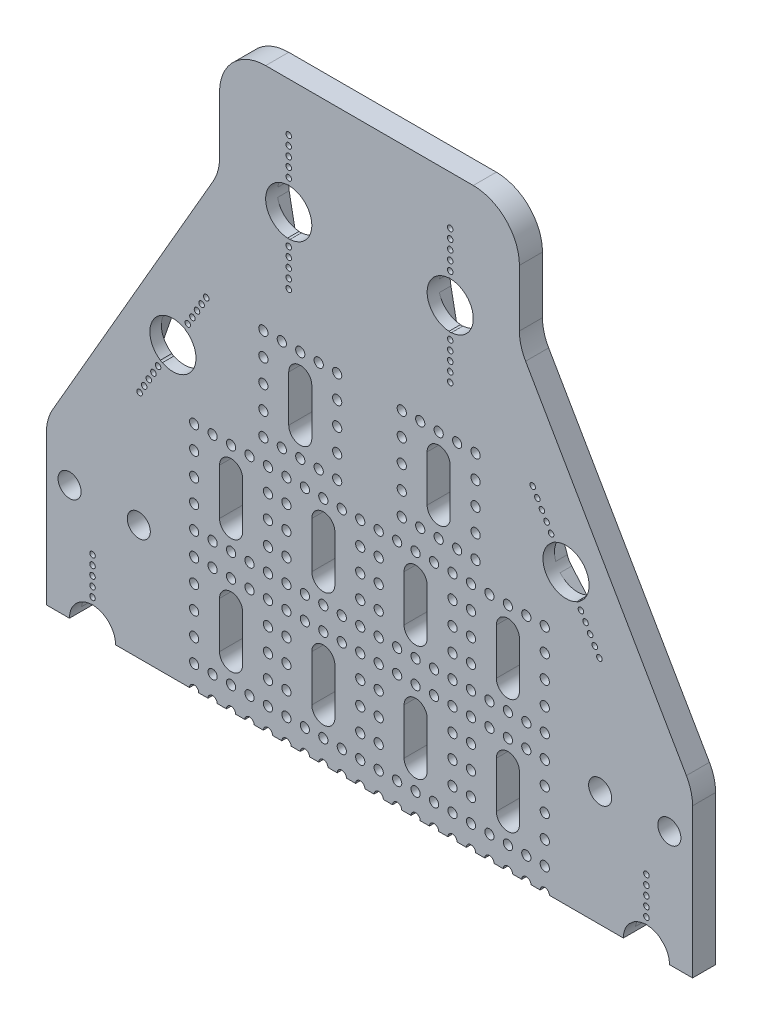
SolidWorks part; units mm, degrees
ref_plane "前视基准面" through (0, 0, 0) normal (0, 0, 1) x (1, 0, 0)
ref_plane "上视基准面" through (0, 0, 0) normal (0, 1, 0) x (1, 0, 0)
ref_plane "右视基准面" through (0, 0, 0) normal (1, 0, 0) x (0, 0, -1)
other "Configuration Table"
sketch "Sketch1" plane through (0, 0, 0) normal (0, 0, 1) x (1, 0, 0)
  line L0 (0, 0) -> (0, 100) construction
  line L1 (-32.5, -100) -> (32.5, -100)
  line L2 (-32.5, -100) -> (-32.5, 100)
  line L3 (-32.5, 100) -> (32.5, 100)
  line L4 (32.5, -100) -> (32.5, 100)
  line L5 (-32.5, -100) -> (32.5, 100) construction
  line L6 (-32.5, 100) -> (32.5, -100) construction
  line L7 (-32.5, 100) -> (-70.0278, 35)
  line L8 (-70.0278, 35) -> (-70.0278, -35)
  line L9 (0, 0) -> (-70.0278, 0) construction
  line L10 (-32.5, -100) -> (-70.0278, -35)
  line L11 (32.5, -100) -> (70.0278, -35)
  line L12 (32.5, 100) -> (70.0278, 35)
  line L13 (70.0278, 35) -> (70.0278, -35)
  point P0 (0, 0)
  dimension "D1" = 65
  dimension "D2" = 200
  dimension "D3" = 35
  dimension "D4" = 30
extrude "Boss-Extrude1" add sketch "Sketch1" along normal mid plane 5 contours L10 L2 L7 L8 | L1 L4 L3 L2 | L13 L12 L4 L11 region at (0, 0, 0) region at (-48.2524, 0, 0) region at (48.2524, 0, 0)
sketch "Sketch2" plane through (0, 0, -2.5) normal (0, 0, -1) x (-1, 0, 0)
  line L0 (0, 0) -> (0, 100) construction
  line L1 (32.5, 100) -> (-32.5, 100) construction
  line L2 (-32.5, 100) -> (-70.0278, 35) construction
  line L3 (-70.0278, 35) -> (-51.2639, 67.5) construction
  line L4 (-51.2639, 67.5) -> (-33.9434, 57.5) construction
  line L5 (-56.7639, 57.9737) -> (-45.7639, 77.0263)
  line L9 (-42.6036, 62.5) -> (-37.1036, 72.0263) construction
  line L10 (0, 0) -> (0, 80) construction
  line L11 (0, 80) -> (20, 80) construction
  line L22 (0, 0) -> (-70.0278, 0) construction
  line L23 (-70.0278, 35) -> (-70.0278, -35) construction
  line L24 (-70.0278, 0) -> (-50.0278, 0) construction
  line L25 (-70.0278, -11) -> (-70.0278, 11)
  line L26 (-70.0278, 11) -> (-50.0278, 11)
  line L27 (-50.0278, 11) -> (-50.0278, 0)
  line L28 (-50.0278, 0) -> (-70.0278, 0) construction
  line L29 (-70.0278, 0) -> (-60.0278, 0) construction
  line L30 (-60.0278, 0) -> (-60.0278, 11) construction
  line L31 (-60.0278, 11) -> (-60.0278, 5.5) construction
  line L32 (-60.0278, 5.5) -> (-50.0278, 5.5) construction
  line L33 (-50.0278, 5.5) -> (-55.0278, 5.5) construction
  line L34 (-50.0278, -5.5) -> (-55.0278, -5.5) construction
  line L35 (-60.0278, -5.5) -> (-50.0278, -5.5) construction
  line L36 (-60.0278, -11) -> (-60.0278, -5.5) construction
  line L37 (-60.0278, 0) -> (-60.0278, -11) construction
  line L38 (-50.0278, -11) -> (-50.0278, 0)
  line L39 (-70.0278, -11) -> (-50.0278, -11)
  circle A8 centre (-55.0278, 5.5) radius 2.5
  circle A9 centre (-55.0278, -5.5) radius 2.5
  circle A10 centre (-65.0278, -5.5) radius 2.5
  circle A11 centre (-65.0278, 5.5) radius 2.5
  circle A84 centre (-42.6036, 62.5) radius 5
  circle A86 centre (-60.0278, 0) radius 5
  circle A87 centre (-42.6036, -62.5) radius 5
  circle A88 centre (42.6036, -62.5) radius 5
  circle A89 centre (60.0278, 0) radius 5
  circle A90 centre (42.6036, 62.5) radius 5
  circle A91 centre (20, 80) radius 5
  circle A93 centre (-20, 80) radius 5
  dimension "D3" = 10
  dimension "D6" = 5
  dimension "D7" = 10
  dimension "D8" = 10
  dimension "D1" = 22
  dimension "D2" = 10
  dimension "D4" = 20
  dimension "D5" = 22
  dimension "D9" = 20
  dimension "D10" = 80
sketch "Sketch3" plane through (0, 0, -2.5) normal (0, 0, -1) x (-1, 0, 0)
  line L0 (0, 0) -> (0, -75) construction
  line L1 (0, -50) -> (0, -75) construction
  line L2 (-25, -100) -> (25, -100)
  line L3 (-25, -100) -> (-25, -50)
  line L4 (-25, -50) -> (25, -50)
  line L5 (25, -100) -> (25, -50)
  line L6 (-25, -100) -> (25, -50) construction
  line L7 (-25, -50) -> (25, -100) construction
  line L8 (0, -75) -> (25, -75) construction
  line L9 (25, -75) -> (12.5, -75) construction
  line L10 (0, -75) -> (17.6777, -57.3223) construction
  circle A4 centre (17.6777, -57.3223) radius 2.5
  circle A5 centre (-17.6777, -57.3223) radius 2.5
  circle A6 centre (17.6777, -92.6777) radius 2.5
  circle A7 centre (-17.6777, -92.6777) radius 2.5
  dimension "D3" = 5
  dimension "D1" = 50
  dimension "D2" = 75
  dimension "D4" = 25
sketch "Sketch5" plane through (0, 0, -2.5) normal (0, 0, -1) x (-1, 0, 0)
  line L0 (0, 0) -> (0, 40) construction
  line L1 (0, 40) -> (30, 40) construction
  line L2 (30, 40) -> (38, 40) construction
  line L3 (27.5, 35) -> (32.5, 35)
  line L4 (27.5, 35) -> (27.5, 45)
  line L5 (27.5, 45) -> (32.5, 45)
  line L6 (32.5, 35) -> (32.5, 45)
  line L7 (27.5, 35) -> (32.5, 45) construction
  line L8 (27.5, 45) -> (32.5, 35) construction
  line L9 (38, 40) -> (38, 50) construction
  line L10 (38, 50) -> (38, 45) construction
  line L11 (30, 40) -> (30, 45) construction
  line L12 (22, 50) -> (22, 45) construction
  line L13 (22, 40) -> (22, 50) construction
  line L14 (22, 50) -> (38, 50) construction
  line L15 (38, 50) -> (30, 50) construction
  line L16 (30, 50) -> (34, 50) construction
  circle A0 centre (30, 45) radius 2.5
  circle A1 centre (30, 35) radius 2.5
  circle A2 centre (38, 50) radius 1
  circle A3 centre (38, 45) radius 1
  circle A4 centre (38, 40) radius 1
  circle A5 centre (38, 35) radius 1
  circle A6 centre (38, 30) radius 1
  circle A7 centre (22, 30) radius 1
  circle A8 centre (22, 35) radius 1
  circle A9 centre (22, 40) radius 1
  circle A10 centre (22, 45) radius 1
  circle A11 centre (22, 50) radius 1
  circle A12 centre (34, 50) radius 1
  circle A13 centre (30, 50) radius 1
  circle A14 centre (26, 50) radius 1
  circle A15 centre (34, 30) radius 1
  circle A16 centre (30, 30) radius 1
  circle A17 centre (26, 30) radius 1
  dimension "D3" = 2
  dimension "D4" = 2
  dimension "D5" = 2
  dimension "D10" = 2
  dimension "D11" = 2
  dimension "D1" = 10
  dimension "D2" = 5
  dimension "D6" = 8
  dimension "D7" = 5
  dimension "D8" = 30
  dimension "D9" = 40
extrude "Cut-Extrude2" cut sketch "Sketch5" against normal blind 5 contours A1 L6 A0 L4 | L5 A0 | A9 | A8 | L3 A1 | L3 A1 | A5 | A3 | A2 | A6 | A14 | A13 | A12 | A15 | A16 | A17 | A0 | A11 | A7 | A4 | A10 region at (-30, 36.061, -2.5) region at (-30, 40, -2.5) region at (-30, 33.939, -2.5) region at (-30, 46.061, -2.5) region at (-38, 50, -2.5) region at (-38, 45, -2.5) region at (-38, 35, -2.5) region at (-38, 30, -2.5) region at (-22, 35, -2.5) region at (-22, 40, -2.5) region at (-34, 50, -2.5) region at (-30, 50, -2.5) region at (-26, 50, -2.5) region at (-34, 30, -2.5) region at (-30, 30, -2.5) region at (-26, 30, -2.5)
pattern_linear "LPattern1" count 4 spacing 20 along (1, 0, 0) of "Cut-Extrude2"
pattern_linear "LPattern2" count 4 spacing 25 along (0, -1, 0) of "LPattern1"
sketch "Sketch9" plane through (0, 0, -2.5) normal (0, 0, -1) x (-1, 0, 0)
  line L0 (-32.5, 100) -> (-32.5, 125)
  line L1 (-32.5, 125) -> (32.5, 125)
  line L2 (32.5, 125) -> (32.5, 100)
  line L3 (-32.5, 100) -> (32.5, 100)
  dimension "D1" = 25
extrude "Boss-Extrude6" add sketch "Sketch9" against normal blind 5
sketch "Sketch12" plane through (0, 0, -2.5) normal (0, 0, -1) x (-1, 0, 0)
  line L0 (-32.5, 125) -> (-32.5, 100) construction
  line L1 (-32.5, 125) -> (-32.5, 100) construction
  line L2 (-32.5, 100) -> (-32.5, 112.5) construction
  line L4 (-32.5, 112.5) -> (-32.5, 125) construction
  line L5 (-32.5, 125) -> (-32.5, 118.75) construction
  line L6 (-32.5, 118.75) -> (-26, 118.75) construction
  line L9 (-26, 118.75) -> (-13, 105.75) construction
  line L10 (-13, 105.75) -> (0, 118.75) construction
  line L11 (0, 118.75) -> (13, 105.75) construction
  line L12 (13, 105.75) -> (26, 118.75) construction
  line L13 (26, 118.75) -> (19.5, 112.25) construction
  circle A23 centre (-26, 118.75) radius 2.5
  circle A24 centre (-26, 105.75) radius 2.5
  circle A25 centre (-13, 118.75) radius 2.5
  circle A26 centre (-13, 105.75) radius 2.5
  circle A27 centre (0, 118.75) radius 2.5
  circle A28 centre (0, 105.75) radius 2.5
  circle A29 centre (13, 118.75) radius 2.5
  circle A30 centre (13, 105.75) radius 2.5
  circle A31 centre (26, 118.75) radius 2.5
  circle A32 centre (26, 105.75) radius 2.5
  circle A33 centre (-19.5, 112.25) radius 2.5
  circle A34 centre (-6.5, 112.25) radius 2.5
  circle A35 centre (6.5, 112.25) radius 2.5
  circle A36 centre (19.5, 112.25) radius 2.5
  dimension "D1" = 5
  dimension "D2" = 6.5
  dimension "D4" = 5
  dimension "D3" = 2
  dimension "D5" = 13
sketch "Sketch13" plane through (0, 0, -2.5) normal (0, 0, -1) x (-1, 0, 0)
  line L0 (0, 0) -> (0, 65) construction
  line L1 (0, 65) -> (15, 65) construction
  line L2 (-15, 75) -> (-19, 75) construction
  line L3 (15, 65) -> (23, 65) construction
  line L4 (12.5, 60) -> (17.5, 60)
  line L5 (12.5, 60) -> (12.5, 70)
  line L6 (12.5, 70) -> (17.5, 70)
  line L7 (17.5, 60) -> (17.5, 70)
  line L8 (12.5, 60) -> (17.5, 70) construction
  line L9 (12.5, 70) -> (17.5, 60) construction
  line L10 (23, 65) -> (23, 75) construction
  line L11 (23, 75) -> (23, 70) construction
  line L12 (15, 65) -> (15, 70) construction
  line L13 (7, 75) -> (7, 70) construction
  line L14 (7, 65) -> (7, 75) construction
  line L15 (7, 75) -> (23, 75) construction
  line L16 (23, 75) -> (15, 75) construction
  line L17 (15, 75) -> (19, 75) construction
  line L18 (-23, 75) -> (-15, 75) construction
  line L19 (-7, 75) -> (-23, 75) construction
  line L20 (-7, 65) -> (-7, 75) construction
  line L21 (-7, 75) -> (-7, 70) construction
  line L22 (-15, 65) -> (-15, 70) construction
  line L23 (-23, 75) -> (-23, 70) construction
  line L24 (-23, 65) -> (-23, 75) construction
  line L25 (-12.5, 70) -> (-17.5, 60) construction
  line L26 (-12.5, 60) -> (-17.5, 70) construction
  line L27 (-15, 65) -> (-23, 65) construction
  line L28 (-17.5, 60) -> (-17.5, 70)
  line L29 (-12.5, 70) -> (-17.5, 70)
  line L30 (-12.5, 60) -> (-12.5, 70)
  line L31 (-12.5, 60) -> (-17.5, 60)
  circle A0 centre (15, 70) radius 2.5
  circle A1 centre (15, 60) radius 2.5
  circle A2 centre (23, 75) radius 1
  circle A3 centre (23, 70) radius 1
  circle A4 centre (23, 65) radius 1
  circle A5 centre (23, 60) radius 1
  circle A6 centre (23, 55) radius 1
  circle A7 centre (7, 55) radius 1
  circle A8 centre (7, 60) radius 1
  circle A9 centre (7, 65) radius 1
  circle A10 centre (7, 70) radius 1
  circle A11 centre (7, 75) radius 1
  circle A12 centre (19, 75) radius 1
  circle A13 centre (15, 75) radius 1
  circle A14 centre (11, 75) radius 1
  circle A15 centre (19, 55) radius 1
  circle A16 centre (15, 55) radius 1
  circle A17 centre (11, 55) radius 1
  circle A18 centre (-11, 55) radius 1
  circle A19 centre (-15, 55) radius 1
  circle A20 centre (-19, 55) radius 1
  circle A21 centre (-11, 75) radius 1
  circle A22 centre (-15, 75) radius 1
  circle A23 centre (-19, 75) radius 1
  circle A24 centre (-7, 75) radius 1
  circle A25 centre (-7, 70) radius 1
  circle A26 centre (-7, 65) radius 1
  circle A27 centre (-7, 60) radius 1
  circle A28 centre (-7, 55) radius 1
  circle A29 centre (-23, 55) radius 1
  circle A30 centre (-23, 60) radius 1
  circle A31 centre (-23, 65) radius 1
  circle A32 centre (-23, 70) radius 1
  circle A33 centre (-23, 75) radius 1
  circle A34 centre (-15, 60) radius 2.5
  circle A35 centre (-15, 70) radius 2.5
  dimension "D3" = 2
  dimension "D4" = 2
  dimension "D5" = 2
  dimension "D9" = 2
  dimension "D10" = 2
  dimension "D1" = 10
  dimension "D2" = 5
  dimension "D6" = 8
  dimension "D7" = 5
  dimension "D8" = 65
  dimension "D11" = 15
extrude "Cut-Extrude5" cut sketch "Sketch13" against normal blind 5 contours A35 L29 | A35 L29 | L30 A35 L28 A34 | A34 L31 | A34 L31 | A33 | A23 | A22 | A21 | A24 | A25 | A32 | A31 | A19 | A18 | A14 | L6 A0 | L6 A0 | A1 L7 A0 L5 | L4 A1 | A5 | A4 | L4 A1 | A16 | A6 | A30 | A29 | A20 | A28 | A27 | A26 | A10 | A11 | A13 | A12 | A2 | A3 | A8 | A7 | A17 | A15 | A9 region at (-15, 61.061, -2.5) region at (-15, 65, -2.5) region at (-15, 58.939, -2.5) region at (-15, 71.061, -2.5) region at (-15, 68.939, -2.5) region at (15, 61.061, -2.5) region at (15, 65, -2.5) region at (15, 58.939, -2.5) region at (15, 71.061, -2.5) region at (15, 68.939, -2.5) region at (-23, 65, -2.5) region at (-23, 60, -2.5) region at (-23, 55, -2.5) region at (-11, 75, -2.5) region at (-15, 55, -2.5) region at (11, 55, -2.5) region at (15, 55, -2.5) region at (11, 75, -2.5) region at (15, 75, -2.5) region at (19, 75, -2.5) region at (7, 75, -2.5) region at (7, 70, -2.5) region at (23, 65, -2.5) region at (23, 70, -2.5) region at (23, 75, -2.5)
fillet "Fillet4" radius 10 10 edges at (70.0278, -35, 0) (-32.5, -100, 0) (32.5, -100, 0) (-70.0278, -35, 0) (-70.0278, 35, 0) (70.0278, 35, 0) (32.5, 100, 0) (-32.5, 100, 0) (-32.5, 125, 0) (32.5, 125, 0)
extrude "Cut-Extrude6" cut sketch "Sketch3" against normal blind 5 contours A4 | A5 | A7 | A6 region at (-17.6777, -57.3223, -2.5) region at (17.6777, -57.3223, -2.5) region at (-17.6777, -92.6777, -2.5) region at (17.6777, -92.6777, -2.5)
sketch "Sketch14" plane through (0, 0, -2.5) normal (0, 0, -1) x (-1, 0, 0)
  line L0 (0, -75) -> (8, -75) construction
  line L1 (-2.5, -80) -> (2.5, -80)
  line L2 (-2.5, -80) -> (-2.5, -70)
  line L3 (-2.5, -70) -> (2.5, -70)
  line L4 (2.5, -80) -> (2.5, -70)
  line L5 (-2.5, -80) -> (2.5, -70) construction
  line L6 (-2.5, -70) -> (2.5, -80) construction
  line L7 (8, -75) -> (8, -65) construction
  line L8 (8, -65) -> (8, -70) construction
  line L9 (0, -75) -> (0, -70) construction
  line L10 (-8, -65) -> (-8, -70) construction
  line L11 (-8, -75) -> (-8, -65) construction
  line L12 (-8, -65) -> (8, -65) construction
  line L13 (8, -65) -> (0, -65) construction
  line L14 (0, -65) -> (4, -65) construction
  line L15 (0, 0) -> (0, -75) construction
  line L16 (8, -85) -> (-8, -85) construction
  circle A0 centre (0, -70) radius 2.5
  circle A1 centre (0, -80) radius 2.5
  circle A2 centre (8, -65) radius 1
  circle A3 centre (8, -70) radius 1
  circle A4 centre (8, -75) radius 1
  circle A5 centre (8, -80) radius 1
  circle A6 centre (8, -85) radius 1
  circle A7 centre (-8, -85) radius 1
  circle A8 centre (-8, -80) radius 1
  circle A9 centre (-8, -75) radius 1
  circle A10 centre (-8, -70) radius 1
  circle A11 centre (-8, -65) radius 1
  circle A12 centre (4, -65) radius 1
  circle A13 centre (0, -65) radius 1
  circle A14 centre (-4, -65) radius 1
  circle A15 centre (4, -85) radius 1
  circle A16 centre (0, -85) radius 1
  circle A17 centre (-4, -85) radius 1
  dimension "D3" = 2
  dimension "D4" = 2
  dimension "D5" = 2
  dimension "D8" = 2
  dimension "D9" = 2
  dimension "D1" = 10
  dimension "D2" = 5
  dimension "D6" = 8
  dimension "D7" = 5
  dimension "D10" = 75
extrude "Cut-Extrude7" cut sketch "Sketch14" against normal blind 5 contours L1 A1 | L1 A1 | A1 L4 A0 L2 | L3 A0 | L3 A0 | A4 | A5 | A6 | A15 | A16 | A17 | A7 | A8 | A9 | A10 | A11 | A12 | A2 | A3 | A14 | A13 region at (0, -78.939, -2.5) region at (0, -75, -2.5) region at (0, -81.061, -2.5) region at (0, -68.939, -2.5) region at (0, -71.061, -2.5) region at (-8, -65, -2.5) region at (-8, -70, -2.5) region at (-8, -75, -2.5) region at (-8, -80, -2.5) region at (-8, -85, -2.5) region at (8, -85, -2.5) region at (8, -80, -2.5) region at (8, -75, -2.5) region at (8, -70, -2.5) region at (8, -65, -2.5) region at (-4, -65, -2.5) region at (-4, -85, -2.5) region at (0, -85, -2.5) region at (4, -85, -2.5)
extrude "Cut-Extrude8" [suppressed] cut sketch "Sketch12" against normal blind 5
extrude "Cut-Extrude9" cut sketch "Sketch2" against normal blind 10 contours A8 A86 A11 A10 A9 | A84 | A90 | A89 | A88 | A87 region at (60.0278, 0, -2.5) region at (42.6036, 62.5, -2.5) region at (42.6036, -62.5, -2.5) region at (-42.6036, -62.5, -2.5) region at (-60.0278, 0, -2.5) region at (-42.6036, 62.5, -2.5)
sketch "Sketch15" plane through (0, 0, -2.5) normal (0, 0, -1) x (-1, 0, 0)
  line L0 (-42.6036, 62.5) -> (-40.3786, 66.3538) construction
  line L1 (-33.8397, 97.6795) -> (-68.688, 37.3205) construction
  line L2 (-42.6036, 62.5) -> (-39.3786, 60.638) construction
  line L3 (-60.0278, 0) -> (-60.0278, 4.45) construction
  line L4 (-60.0278, 0) -> (-52.7095, 0) construction
  line L5 (-42.6036, -62.5) -> (-44.8286, -58.6462) construction
  line L6 (-35.3868, -95) -> (-68.688, -37.3205) construction
  line L7 (-44.8286, -58.6462) -> (-45.8286, -56.9141) construction
  line L8 (-42.6036, -62.5) -> (-38.2735, -60) construction
  line L9 (-40.3786, -66.3538) -> (-39.3786, -68.0859) construction
  line L10 (0, 125) -> (0, -100) construction
  line L11 (22.5, 125) -> (-22.5, 125) construction
  line L12 (26.7265, -100) -> (-26.7265, -100) construction
  line L13 (40.3786, -66.3538) -> (39.3786, -68.0859) construction
  line L14 (42.6036, -62.5) -> (38.2735, -60) construction
  line L15 (44.8286, -58.6462) -> (45.8286, -56.9141) construction
  line L16 (42.6036, -62.5) -> (44.8286, -58.6462) construction
  line L17 (60.0278, 0) -> (52.7095, 0) construction
  line L18 (60.0278, 0) -> (60.0278, 4.45) construction
  line L19 (42.6036, 62.5) -> (39.3786, 60.638) construction
  line L20 (42.6036, 62.5) -> (40.3786, 66.3538) construction
  circle A0 centre (-40.3786, 66.3538) radius 0.6
  circle A1 centre (-39.3786, 68.0859) radius 0.6
  circle A2 centre (-38.3786, 69.8179) radius 0.6
  circle A3 centre (-37.3786, 71.55) radius 0.6
  circle A4 centre (-36.3786, 73.282) radius 0.6
  circle A5 centre (-35.3786, 75.0141) radius 0.6
  circle A6 centre (-49.8286, 49.9859) radius 0.6
  circle A7 centre (-48.8286, 51.718) radius 0.6
  circle A8 centre (-47.8286, 53.45) radius 0.6
  circle A9 centre (-46.8286, 55.1821) radius 0.6
  circle A10 centre (-45.8286, 56.9141) radius 0.6
  circle A11 centre (-44.8286, 58.6462) radius 0.6
  circle A12 centre (-60.0278, 4.45) radius 0.6
  circle A13 centre (-60.0278, 6.45) radius 0.6
  circle A14 centre (-60.0278, 8.45) radius 0.6
  circle A15 centre (-60.0278, 10.45) radius 0.6
  circle A16 centre (-60.0278, 12.45) radius 0.6
  circle A17 centre (-60.0278, 14.45) radius 0.6
  circle A18 centre (-60.0278, -14.45) radius 0.6
  circle A19 centre (-60.0278, -12.45) radius 0.6
  circle A20 centre (-60.0278, -10.45) radius 0.6
  circle A21 centre (-60.0278, -8.45) radius 0.6
  circle A22 centre (-60.0278, -6.45) radius 0.6
  circle A23 centre (-60.0278, -4.45) radius 0.6
  circle A24 centre (-44.8286, -58.6462) radius 0.6
  circle A25 centre (-45.8286, -56.9141) radius 0.6
  circle A26 centre (-46.8286, -55.1821) radius 0.6
  circle A27 centre (-47.8286, -53.45) radius 0.6
  circle A28 centre (-48.8286, -51.718) radius 0.6
  circle A29 centre (-49.8286, -49.9859) radius 0.6
  circle A30 centre (-42.6036, -62.5) radius 5 construction
  circle A31 centre (-35.3786, -75.0141) radius 0.6
  circle A32 centre (-36.3786, -73.282) radius 0.6
  circle A33 centre (-37.3786, -71.55) radius 0.6
  circle A34 centre (-38.3786, -69.8179) radius 0.6
  circle A35 centre (-39.3786, -68.0859) radius 0.6
  circle A36 centre (-40.3786, -66.3538) radius 0.6
  circle A37 centre (40.3786, -66.3538) radius 0.6
  circle A38 centre (39.3786, -68.0859) radius 0.6
  circle A39 centre (38.3786, -69.8179) radius 0.6
  circle A40 centre (37.3786, -71.55) radius 0.6
  circle A41 centre (36.3786, -73.282) radius 0.6
  circle A42 centre (35.3786, -75.0141) radius 0.6
  circle A43 centre (49.8286, -49.9859) radius 0.6
  circle A44 centre (48.8286, -51.718) radius 0.6
  circle A45 centre (47.8286, -53.45) radius 0.6
  circle A46 centre (46.8286, -55.1821) radius 0.6
  circle A47 centre (45.8286, -56.9141) radius 0.6
  circle A48 centre (44.8286, -58.6462) radius 0.6
  circle A49 centre (60.0278, -4.45) radius 0.6
  circle A50 centre (60.0278, -6.45) radius 0.6
  circle A51 centre (60.0278, -8.45) radius 0.6
  circle A52 centre (60.0278, -10.45) radius 0.6
  circle A53 centre (60.0278, -12.45) radius 0.6
  circle A54 centre (60.0278, -14.45) radius 0.6
  circle A55 centre (60.0278, 14.45) radius 0.6
  circle A56 centre (60.0278, 12.45) radius 0.6
  circle A57 centre (60.0278, 10.45) radius 0.6
  circle A58 centre (60.0278, 8.45) radius 0.6
  circle A59 centre (60.0278, 6.45) radius 0.6
  circle A60 centre (60.0278, 4.45) radius 0.6
  circle A61 centre (44.8286, 58.6462) radius 0.6
  circle A62 centre (45.8286, 56.9141) radius 0.6
  circle A63 centre (46.8286, 55.1821) radius 0.6
  circle A64 centre (47.8286, 53.45) radius 0.6
  circle A65 centre (48.8286, 51.718) radius 0.6
  circle A66 centre (49.8286, 49.9859) radius 0.6
  circle A67 centre (35.3786, 75.0141) radius 0.6
  circle A68 centre (36.3786, 73.282) radius 0.6
  circle A69 centre (37.3786, 71.55) radius 0.6
  circle A70 centre (38.3786, 69.8179) radius 0.6
  circle A71 centre (39.3786, 68.0859) radius 0.6
  circle A72 centre (40.3786, 66.3538) radius 0.6
  dimension "D2" = 1.2
  dimension "D5" = 1.2
  dimension "D6" = 2
  dimension "D8" = 1.2
  dimension "D1" = 4.45
  dimension "D4" = 4.45
  dimension "D9" = 4.45
  dimension "D11" = 2
  dimension "D12" = 2
  dimension "D3" = 6
  dimension "D7" = 6
  dimension "D10" = 6
extrude "Cut-Extrude10" cut sketch "Sketch15" against normal blind 10
sketch "Sketch16" plane through (0, 0, -2.5) normal (0, 0, -1) x (-1, 0, 0)
  line L0 (-46.3788, 65.7784) -> (-37.0775, 76.4893)
  line L1 (-33.2516, 74.2805) -> (-37.8769, 60.8698)
  line L2 (-42.6036, 62.5) -> (-49.3484, 66.3941) construction
  line L3 (-48.1298, 48.5107) -> (-38.8284, 59.2216)
  line L4 (-47.3304, 64.1302) -> (-51.9557, 50.7195)
  line L5 (-62.2366, 14.8782) -> (-64.9364, 0.9516)
  line L6 (-60.0278, -14.45) -> (-60.0278, 14.45) construction
  line L7 (-57.8189, 14.8782) -> (-55.1191, 0.9516)
  line L8 (-60.0278, 0) -> (-49.3484, 0) construction
  line L9 (-57.8189, -14.8782) -> (-55.1191, -0.9516)
  line L10 (-62.2366, -14.8782) -> (-64.9364, -0.9516)
  line L11 (-42.6036, -62.5) -> (-49.3484, -66.3941) construction
  line L12 (-47.3304, -64.1302) -> (-51.9557, -50.7195)
  line L13 (-48.1298, -48.5107) -> (-38.8284, -59.2216)
  line L14 (-33.2516, -74.2805) -> (-37.8769, -60.8698)
  line L15 (-46.3788, -65.7784) -> (-37.0775, -76.4893)
  line L16 (0, 0) -> (0, -100) construction
  line L17 (26.7265, -100) -> (-26.7265, -100) construction
  line L18 (42.6036, -62.5) -> (49.3484, -66.3941) construction
  line L19 (60.0278, 0) -> (49.3484, 0) construction
  line L20 (60.0278, -14.45) -> (60.0278, 14.45) construction
  line L21 (42.6036, 62.5) -> (49.3484, 66.3941) construction
  line L22 (46.3788, -65.7784) -> (37.0775, -76.4893)
  line L23 (33.2516, -74.2805) -> (37.8769, -60.8698)
  line L24 (48.1298, -48.5107) -> (38.8284, -59.2216)
  line L25 (47.3304, -64.1302) -> (51.9557, -50.7195)
  line L26 (62.2366, -14.8782) -> (64.9364, -0.9516)
  line L27 (57.8189, -14.8782) -> (55.1191, -0.9516)
  line L28 (57.8189, 14.8782) -> (55.1191, 0.9516)
  line L29 (62.2366, 14.8782) -> (64.9364, 0.9516)
  line L30 (47.3304, 64.1302) -> (51.9557, 50.7195)
  line L31 (48.1298, 48.5107) -> (38.8284, 59.2216)
  line L32 (33.2516, 74.2805) -> (37.8769, 60.8698)
  line L33 (46.3788, 65.7784) -> (37.0775, 76.4893)
  circle A0 centre (-42.6036, 62.5) radius 5
  circle A1 centre (-35.3786, 75.0141) radius 2.25
  arc A2 (-44.8803, 58.0484) -> (-39.8868, 66.6975) centre (-42.6036, 62.5) ccw construction
  circle A3 centre (-49.8286, 49.9859) radius 2.25
  circle A4 centre (-60.0278, 0) radius 5
  circle A5 centre (-60.0278, 14.45) radius 2.25
  arc A6 (-57.0278, 4) -> (-59.7737, 4.9935) centre (-60.0278, 0) ccw construction
  circle A7 centre (-60.0278, -14.45) radius 2.25
  circle A8 centre (-49.8286, -49.9859) radius 2.25
  circle A9 centre (-35.3786, -75.0141) radius 2.25
  circle A10 centre (-42.6036, -62.5) radius 5
  circle A11 centre (42.6036, -62.5) radius 5
  circle A12 centre (35.3786, -75.0141) radius 2.25
  circle A13 centre (49.8286, -49.9859) radius 2.25
  circle A14 centre (60.0278, -14.45) radius 2.25
  circle A15 centre (60.0278, 14.45) radius 2.25
  circle A16 centre (60.0278, 0) radius 5
  circle A17 centre (49.8286, 49.9859) radius 2.25
  circle A18 centre (35.3786, 75.0141) radius 2.25
  circle A19 centre (42.6036, 62.5) radius 5
  dimension "D1" = 4.5
  dimension "D2" = 4.5
extrude "Cut-Extrude11" cut sketch "Sketch16" against normal blind 2.5 contours L4 A3 L3 A0 | A0 | A1 L0 A0 L1 | A1 | A3 | A5 L5 A4 L7 | A5 | A4 | L10 A7 L9 A4 | A7 | A8 | L12 A10 L13 A8 | A10 | L14 A10 L15 A9 | A9 | A12 L22 A11 L23 | A12 | A11 | L25 A13 L24 A11 | A13 | L26 A16 L27 A14 | A14 | A16 | L28 A16 L29 A15 | A15 | L30 A19 L31 A17 | A17 | L32 A19 L33 A18 | A19 | A18 A3 region at (38.5407, 69.5372, -2.5) region at (42.6036, 62.5, -2.5) region at (35.3786, 75.0141, -2.5) region at (46.6666, 55.4628, -2.5) region at (49.8286, 49.9859, -2.5) region at (60.0278, 8.1259, -2.5) region at (60.0278, 14.45, -2.5) region at (60.0278, 0, -2.5) region at (60.0278, -8.1259, -2.5) region at (60.0278, -14.45, -2.5) region at (46.6666, -55.4628, -2.5) region at (42.6036, -62.5, -2.5) region at (49.8286, -49.9859, -2.5) region at (38.5407, -69.5372, -2.5) region at (35.3786, -75.0141, -2.5) region at (-38.5407, -69.5372, -2.5) region at (-42.6036, -62.5, -2.5) region at (-35.3786, -75.0141, -2.5) region at (-46.6666, -55.4628, -2.5) region at (-49.8286, -49.9859, -2.5) region at (-60.0278, -8.1259, -2.5) region at (-60.0278, -14.45, -2.5) region at (-60.0278, 0, -2.5) region at (-60.0278, 8.1259, -2.5) region at (-60.0278, 14.45, -2.5) region at (-46.6666, 55.4628, -2.5) region at (-42.6036, 62.5, -2.5) region at (-49.8286, 49.9859, -2.5) region at (-38.5407, 69.5372, -2.5) region at (-35.3786, 75.0141, -2.5)
sketch "Sketch20" plane through (0, 0, -2.5) normal (0, 0, -1) x (-1, 0, 0)
  line L0 (0, 0) -> (0, 100) construction
  line L1 (0, 100) -> (17.5, 100) construction
  circle A0 centre (17.5, 100) radius 5
  circle A1 centre (-17.5, 100) radius 5
  dimension "D1" = 10
  dimension "D2" = 17.5
  dimension "D3" = 100
extrude "Cut-Extrude12" cut sketch "Sketch20" against normal through all
sketch "Sketch21" plane through (0, 0, -2.5) normal (0, 0, -1) x (-1, 0, 0)
  line L0 (-17.5, 100) -> (-17.5, 104.45) construction
  line L1 (-17.5, 104.45) -> (-17.5, 106.45) construction
  line L2 (-17.5, 100) -> (-12.5, 100) construction
  line L3 (-17.5, 95.55) -> (-17.5, 93.55) construction
  line L4 (0, 0) -> (0, 125) construction
  line L5 (22.5, 125) -> (-22.5, 125) construction
  line L6 (17.5, 95.55) -> (17.5, 93.55) construction
  line L7 (17.5, 100) -> (12.5, 100) construction
  line L8 (17.5, 104.45) -> (17.5, 106.45) construction
  line L9 (17.5, 100) -> (17.5, 104.45) construction
  circle A0 centre (-17.5, 104.45) radius 0.6
  circle A1 centre (-17.5, 106.45) radius 0.6
  circle A2 centre (-17.5, 108.45) radius 0.6
  circle A3 centre (-17.5, 110.45) radius 0.6
  circle A4 centre (-17.5, 112.45) radius 0.6
  circle A5 centre (-17.5, 114.45) radius 0.6
  circle A6 centre (-17.5, 100) radius 5 construction
  circle A7 centre (-17.5, 85.55) radius 0.6
  circle A8 centre (-17.5, 87.55) radius 0.6
  circle A9 centre (-17.5, 89.55) radius 0.6
  circle A10 centre (-17.5, 91.55) radius 0.6
  circle A11 centre (-17.5, 93.55) radius 0.6
  circle A12 centre (-17.5, 95.55) radius 0.6
  circle A25 centre (17.5, 95.55) radius 0.6
  circle A26 centre (17.5, 93.55) radius 0.6
  circle A27 centre (17.5, 91.55) radius 0.6
  circle A28 centre (17.5, 89.55) radius 0.6
  circle A29 centre (17.5, 87.55) radius 0.6
  circle A30 centre (17.5, 85.55) radius 0.6
  circle A31 centre (17.5, 114.45) radius 0.6
  circle A32 centre (17.5, 112.45) radius 0.6
  circle A33 centre (17.5, 110.45) radius 0.6
  circle A34 centre (17.5, 108.45) radius 0.6
  circle A35 centre (17.5, 106.45) radius 0.6
  circle A36 centre (17.5, 104.45) radius 0.6
  dimension "D2" = 1.2
  dimension "D1" = 4.45
  dimension "D4" = 2
  dimension "D3" = 6
extrude "Cut-Extrude13" cut sketch "Sketch21" against normal through all
sketch "Sketch22" plane through (0, 0, -2.5) normal (0, 0, -1) x (-1, 0, 0)
  line L0 (-19.7089, 114.8782) -> (-22.4086, 100.9516)
  line L1 (-17.5, 100) -> (-17.5, 114.45) construction
  line L2 (-15.2592, 114.6538) -> (-12.5407, 100.637)
  line L3 (-17.5, 100) -> (-12.5, 100) construction
  line L4 (-15.2592, 85.3462) -> (-12.5407, 99.363)
  line L5 (-22.6007, 100.0394) -> (-18.9481, 81.1971)
  line L6 (0, 0) -> (0, 125) construction
  line L7 (22.5, 125) -> (-22.5, 125) construction
  line L8 (17.5, 100) -> (12.5, 100) construction
  line L9 (17.5, 100) -> (17.5, 114.45) construction
  line L10 (22.6449, 100.2674) -> (18.8413, 80.6461)
  line L11 (15.2592, 85.3462) -> (12.5407, 99.363)
  line L12 (15.2592, 114.6538) -> (12.5407, 100.637)
  line L13 (19.7089, 114.8782) -> (22.4086, 100.9516)
  circle A0 centre (-17.5, 100) radius 5
  circle A1 centre (-17.5, 114.45) radius 2.25
  arc A2 (-17.7541, 104.9935) -> (-17.7541, 95.0065) centre (-17.5, 100) ccw construction
  circle A3 centre (-17.5, 85.55) radius 2.25
  circle A4 centre (17.5, 85.55) radius 2.25
  circle A5 centre (17.5, 114.45) radius 2.25
  circle A6 centre (17.5, 100) radius 5
  dimension "D1" = 4.5
extrude "Cut-Extrude14" cut sketch "Sketch22" against normal blind 2.5 contours A1 L0 A0 L2 | A1 | A3 L4 A0 | A3 | A6 L11 A4 | A4 | L12 A6 L13 A5 | A5 L0 region at (17.5089, 108.126, -2.5) region at (17.5, 114.45, -2.5) region at (17.5089, 91.874, -2.5) region at (17.5, 85.55, -2.5) region at (-17.5089, 91.874, -2.5) region at (-17.5, 85.55, -2.5) region at (-17.5089, 108.126, -2.5) region at (-17.5, 114.45, -2.5)
sketch "Sketch23" plane through (0, 0, -2.5) normal (0, 0, -1) x (-1, 0, 0)
  line L0 (0, 0) -> (-57.5, 0) construction
  line L1 (-57.5, 0) -> (-57.5, 25) construction
  line L2 (-57.5, 25) -> (-50, 25) construction
  line L3 (0, 0) -> (0, 18.2627) construction
  line L4 (57.5, 25) -> (50, 25) construction
  line L5 (57.5, 0) -> (57.5, 25) construction
  circle A1 centre (-50, 25) radius 2.5
  circle A2 centre (-65, 25) radius 2.5
  circle A3 centre (-50, -25) radius 2.5
  circle A4 centre (-65, -25) radius 2.5
  circle A5 centre (65, -25) radius 2.5
  circle A6 centre (50, -25) radius 2.5
  circle A7 centre (65, 25) radius 2.5
  circle A8 centre (50, 25) radius 2.5
  dimension "D1" = 57.5
  dimension "D2" = 5
  dimension "D3" = 7.5
  dimension "D4" = 25
extrude "Cut-Extrude15" cut sketch "Sketch23" against normal through all
sketch "Sketch24" plane through (0, 0, -2.5) normal (0, 0, -1) x (-1, 0, 0)
  line L10 (-70.0278, 0) -> (70.0278, 0)
  line L20 (-70.0278, 32.3205) -> (-70.0278, -32.3205)
  line L21 (-68.688, -37.3205) -> (-35.3868, -95)
  line L22 (-26.7265, -100) -> (26.7265, -100)
  line L23 (35.3868, -95) -> (68.688, -37.3205)
  line L24 (70.0278, -32.3205) -> (70.0278, 32.3205)
  line L25 (68.688, 37.3205) -> (33.8397, 97.6795)
  line L26 (32.5, 102.6795) -> (32.5, 115)
  line L27 (22.5, 125) -> (-22.5, 125)
  line L28 (-32.5, 115) -> (-32.5, 102.6795)
  line L29 (-33.8397, 97.6795) -> (-68.688, 37.3205)
  line L30 (-70.0278, 32.3205) -> (-70.0278, -32.3205)
  line L31 (-68.688, -37.3205) -> (-35.3868, -95)
  line L32 (-26.7265, -100) -> (26.7265, -100)
  line L33 (35.3868, -95) -> (68.688, -37.3205)
  line L34 (70.0278, -32.3205) -> (70.0278, 32.3205)
  line L35 (68.688, 37.3205) -> (33.8397, 97.6795)
  line L36 (32.5, 102.6795) -> (32.5, 115)
  line L37 (22.5, 125) -> (-22.5, 125)
  line L38 (-32.5, 115) -> (-32.5, 102.6795)
  line L39 (-33.8397, 97.6795) -> (-68.688, 37.3205)
  arc A20 (-70.0278, -32.3205) -> (-68.688, -37.3205) centre (-60.0278, -32.3205) ccw
  arc A21 (-35.3868, -95) -> (-26.7265, -100) centre (-26.7265, -90) ccw
  arc A22 (26.7265, -100) -> (35.3868, -95) centre (26.7265, -90) ccw
  arc A23 (68.688, -37.3205) -> (70.0278, -32.3205) centre (60.0278, -32.3205) ccw
  arc A24 (70.0278, 32.3205) -> (68.688, 37.3205) centre (60.0278, 32.3205) ccw
  arc A25 (32.5, 102.6795) -> (33.8397, 97.6795) centre (42.5, 102.6795) ccw
  arc A26 (32.5, 115) -> (22.5, 125) centre (22.5, 115) ccw
  arc A27 (-22.5, 125) -> (-32.5, 115) centre (-22.5, 115) ccw
  arc A28 (-33.8397, 97.6795) -> (-32.5, 102.6795) centre (-42.5, 102.6795) ccw
  arc A29 (-68.688, 37.3205) -> (-70.0278, 32.3205) centre (-60.0278, 32.3205) ccw
  arc A30 (-70.0278, -32.3205) -> (-68.688, -37.3205) centre (-60.0278, -32.3205) ccw
  arc A31 (-35.3868, -95) -> (-26.7265, -100) centre (-26.7265, -90) ccw
  arc A32 (26.7265, -100) -> (35.3868, -95) centre (26.7265, -90) ccw
  arc A33 (68.688, -37.3205) -> (70.0278, -32.3205) centre (60.0278, -32.3205) ccw
  arc A34 (70.0278, 32.3205) -> (68.688, 37.3205) centre (60.0278, 32.3205) ccw
  arc A35 (32.5, 102.6795) -> (33.8397, 97.6795) centre (42.5, 102.6795) ccw
  arc A36 (32.5, 115) -> (22.5, 125) centre (22.5, 115) ccw
  arc A37 (-22.5, 125) -> (-32.5, 115) centre (-22.5, 115) ccw
  arc A38 (-33.8397, 97.6795) -> (-32.5, 102.6795) centre (-42.5, 102.6795) ccw
  arc A39 (-68.688, 37.3205) -> (-70.0278, 32.3205) centre (-60.0278, 32.3205) ccw
  dimension "D1" = 0
extrude "Cut-Extrude16" cut sketch "Sketch24" against normal blind 10 contours L33 A33 L34 L10 L30 A30 L31 A31 L32 A32 region at (0, -43.9744, -2.5)
